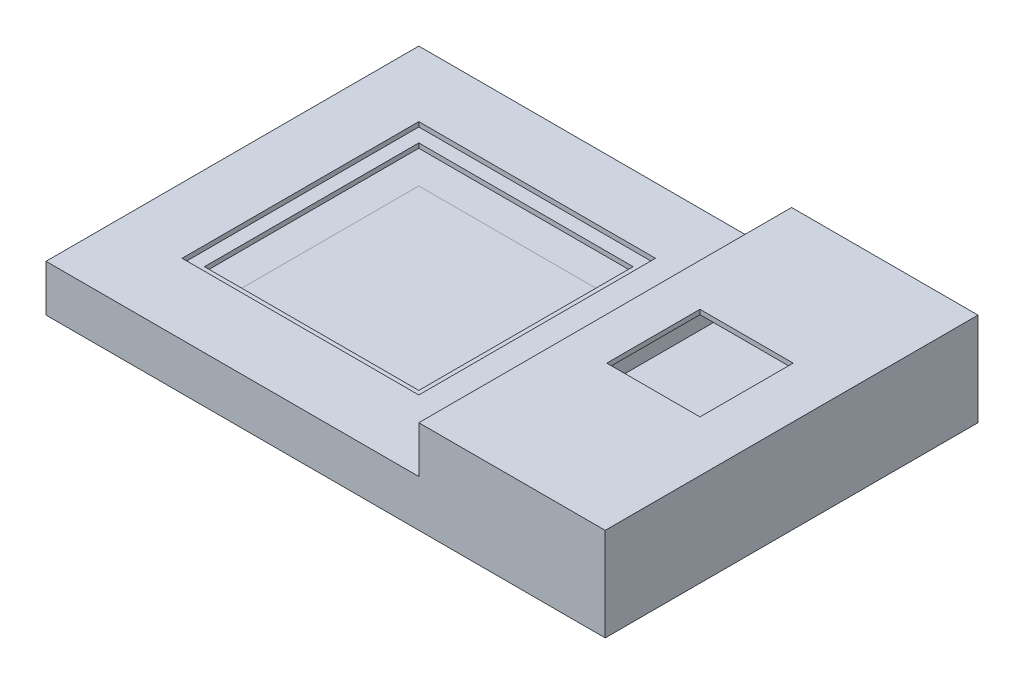
SolidWorks part; units mm, degrees
ref_plane "Front Plane" through (0, 0, 0) normal (0, 0, 1) x (1, 0, 0)
ref_plane "Top Plane" through (0, 0, 0) normal (0, 1, 0) x (1, 0, 0)
ref_plane "Right Plane" through (0, 0, 0) normal (1, 0, 0) x (0, 0, -1)
sketch "Sketch1" plane through (0, 0, 0) normal (0, 1, 0) x (1, 0, 0)
  line L1 (-20, -20) -> (20, -20)
  line L2 (-20, -20) -> (-20, 20)
  line L3 (-20, 20) -> (20, 20)
  line L4 (20, -20) -> (20, 20)
  line L5 (-20, -20) -> (20, 20) construction
  line L6 (-20, 20) -> (20, -20) construction
  line L7 (-11.5, -11.5) -> (11.5, -11.5)
  line L8 (-11.5, -11.5) -> (-11.5, 11.5)
  line L9 (-11.5, 11.5) -> (11.5, 11.5)
  line L10 (11.5, -11.5) -> (11.5, 11.5)
  line L11 (-11.5, -11.5) -> (11.5, 11.5) construction
  line L12 (-11.5, 11.5) -> (11.5, -11.5) construction
  line L13 (20, 20) -> (40, 20)
  line L14 (20, 20) -> (20, -20)
  line L15 (20, -20) -> (40, -20)
  line L16 (40, 20) -> (40, -20)
  point P0 (0, 0)
  point P6 (0, 0)
  point P13 (29.5459, 0.6229)
  dimension "D1" = 40
  dimension "D2" = 40
  dimension "D3" = 23
  dimension "D4" = 23
  dimension "D5" = 20
extrude "Boss-Extrude1" add sketch "Sketch1" against normal blind 5 contours L1 L4 L3 L2 L10 L7 L8 L9 region at (-19.4343, 0, 0)
extrude "Boss-Extrude2" add sketch "Sketch1<4>" against normal blind 5 and the other way blind 5 contours L13 L16 L15 L4
sketch "Sketch1<4>" plane through (0, 0, 0) normal (0, 1, 0) x (1, 0, 0) same geometry as "Sketch1"
sketch "Sketch2" plane through (0, 0, 0) normal (0, 1, 0) x (1, 0, 0)
  line L0 (-20, 20) -> (20, -20) construction
  line L1 (-12.9784, 12.9784) -> (12.4216, 12.9784)
  line L2 (-12.9784, 12.9784) -> (-12.9784, -12.4216)
  line L3 (-12.9784, -12.4216) -> (12.4216, -12.4216)
  line L4 (12.4216, 12.9784) -> (12.4216, -12.4216)
  dimension "D1" = 25.4
extrude "Cut-Extrude1" cut sketch "Sketch2" against normal blind 0.5
sketch "Sketch3" plane through (0, 0, 0) normal (0, 0, 1) x (1, 0, 0)
  line L0 (-20, -5) -> (-20, 0) construction
  line L1 (39.5, -1) -> (-19.5, -1)
  line L2 (39.5, -1) -> (39.5, -4.5)
  line L3 (39.5, -4.5) -> (-19.5, -4.5)
  line L4 (-19.5, -1) -> (-19.5, -4.5)
  line L5 (-20, 0) -> (20, 0) construction
  line L6 (-20, -5) -> (40, -5) construction
  line L7 (40, -5) -> (40, 5) construction
  dimension "D1" = 0.5
  dimension "D2" = 1
  dimension "D3" = 0.5
  dimension "D4" = 0.5
extrude "Cut-Extrude2" cut sketch "Sketch3" against normal blind 19.5 and the other way blind 19.5
sketch "Sketch4" plane through (0, 5, 0) normal (0, 1, 0) x (1, 0, 0)
  line L1 (24.5459, 5.6229) -> (34.5459, 5.6229)
  line L2 (24.5459, 5.6229) -> (24.5459, -4.3771)
  line L3 (24.5459, -4.3771) -> (34.5459, -4.3771)
  line L4 (34.5459, 5.6229) -> (34.5459, -4.3771)
  line L5 (24.5459, 5.6229) -> (34.5459, -4.3771) construction
  line L6 (24.5459, -4.3771) -> (34.5459, 5.6229) construction
  point P0 (29.5459, 0.6229)
  dimension "D1" = 10
  dimension "D2" = 10
sketch "Sketch5" plane through (0, 0, 0) normal (0, 0, 1) x (1, 0, 0)
  line L0 (20, 0) -> (40, 0) construction
  line L1 (39.5, -4.5) -> (20.5, -4.5)
  line L2 (39.5, -4.5) -> (39.5, 4.5)
  line L3 (39.5, 4.5) -> (20.5, 4.5)
  line L4 (20.5, 4.5) -> (20.5, -1)
  line L5 (39.5, -4.5) -> (20.5, 4.5) construction
  line L6 (39.5, 4.5) -> (20.5, -4.5) construction
  line L7 (20, 5) -> (40, 5) construction
  line L8 (40, 5) -> (40, -5) construction
  line L9 (20.5, -1) -> (20, -1)
  line L10 (20.5, -4.5) -> (20, -4.5)
  line L11 (-20, 0) -> (20, 0) construction
  line L12 (-20, -5) -> (40, -5) construction
  line L13 (20, -4.5) -> (20, -1)
  point P0 (30, 0)
  point P11 (0, 0)
  dimension "D1" = 0.5
  dimension "D2" = 0.5
  dimension "D3" = 1
  dimension "D5" = 0.5
extrude "Cut-Extrude3" cut sketch "Sketch5" against normal blind 19.5 and the other way blind 19.5
extrude "Cut-Extrude4" cut sketch "Sketch4" against normal blind 2
sketch "Sketch7" plane through (0, -4.5, 0) normal (0, 1, 0) x (1, 0, 0)
  line L1 (-11.5, -11.5) -> (11.5, -11.5)
  line L2 (-11.5, -11.5) -> (-11.5, 11.5)
  line L3 (-11.5, 11.5) -> (11.5, 11.5)
  line L4 (11.5, -11.5) -> (11.5, 11.5)
  line L5 (-11.5, -11.5) -> (11.5, 11.5) construction
  line L6 (-11.5, 11.5) -> (11.5, -11.5) construction
  point P0 (0, 0)
extrude "Boss-Extrude3" add sketch "Sketch7" against normal blind 0.5 separate body
